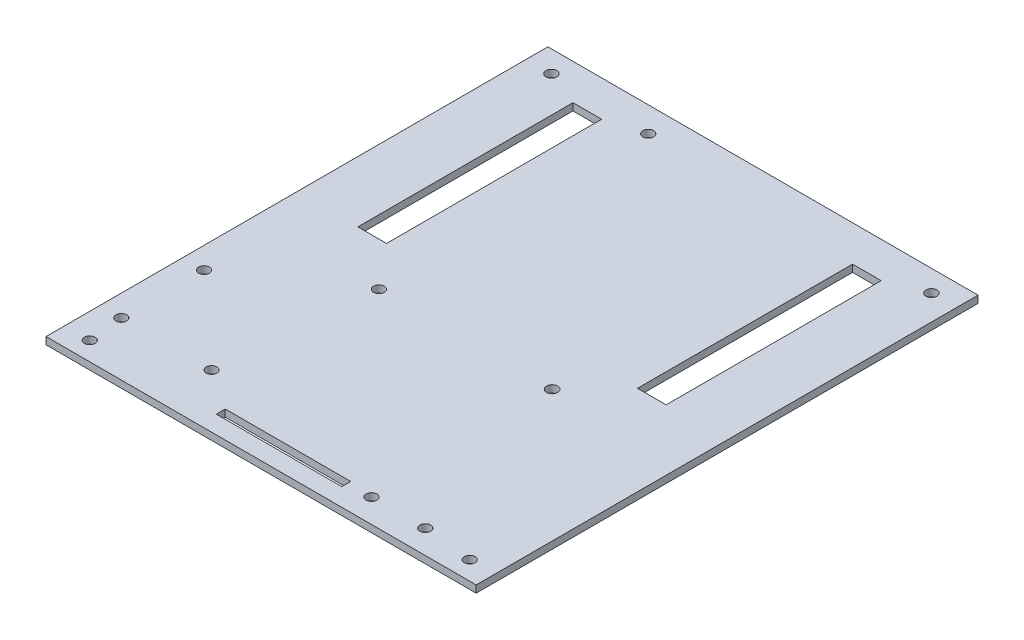
SolidWorks part; units mm, degrees
ref_plane "Front Plane" through (0, 0, 0) normal (0, 0, 1) x (1, 0, 0)
ref_plane "Top Plane" through (0, 0, 0) normal (0, 1, 0) x (1, 0, 0)
ref_plane "Right Plane" through (0, 0, 0) normal (1, 0, 0) x (0, 0, -1)
sketch "Sketch1" plane through (0, 0, 0) normal (0, 1, 0) x (1, 0, 0)
  line L1 (60, -70) -> (-60, -70)
  line L2 (60, -70) -> (60, 70)
  line L3 (60, 70) -> (-60, 70)
  line L4 (-60, -70) -> (-60, 70)
  line L5 (60, -70) -> (-60, 70) construction
  line L6 (60, 70) -> (-60, -70) construction
  point P0 (0, 0)
  dimension "D1" = 140
  dimension "D2" = 120
extrude "Boss-Extrude1" add sketch "Sketch1" along normal blind 2
sketch "Sketch2" plane through (0, 2, 0) normal (0, 1, 0) x (1, 0, 0)
  line L0 (0, 0) -> (0, 70) construction
  line L1 (60, 70) -> (-60, 70) construction
  line L2 (0, 0) -> (-60, 0) construction
  line L3 (-60, 70) -> (-60, -70) construction
  line L4 (-60, -70) -> (60, -70) construction
  circle A0 centre (-53, 64) radius 1.525
  circle A1 centre (-53, -64.8) radius 1.5
  circle A2 centre (53, 64) radius 1.525
  circle A3 centre (53, -64.8) radius 1.5
  dimension "D1" = 3.05
  dimension "D2" = 6
  dimension "D3" = 7
  dimension "D4" = 3
  dimension "D5" = 5.2
  dimension "D6" = 7
extrude "Cut-Extrude1" cut sketch "Sketch2" against normal blind 2
sketch "Sketch4" plane through (0, 2, 0) normal (0, 1, 0) x (1, 0, 0)
  line L0 (60, 70) -> (-60, 70) construction
  line L1 (-60, 70) -> (-60, -70) construction
  line L2 (0, 0) -> (0, 70) construction
  line L3 (-35, 60) -> (-43, 60)
  line L4 (-35, 60) -> (-35, 0)
  line L5 (-35, 0) -> (-43, 0)
  line L6 (-43, 60) -> (-43, 0)
  line L7 (-35, 60) -> (-43, 0) construction
  line L8 (-35, 0) -> (-43, 60) construction
  line L9 (35, 0) -> (43, 0)
  line L10 (35, 60) -> (35, 0)
  line L11 (43, 60) -> (43, 0)
  line L12 (35, 60) -> (43, 60)
  circle A0 centre (-25, 63) radius 1.5
  circle A1 centre (-25, -12.13) radius 1.5
  circle A2 centre (23.33, -12.13) radius 1.55
  point P10 (-39, 30)
  dimension "D1" = 3
  dimension "D2" = 3
  dimension "D4" = 7
  dimension "D5" = 35
  dimension "D6" = 35
  dimension "D7" = 3.1
  dimension "D9" = 82.13
  dimension "D3" = 75.13
  dimension "D8" = 48.33
  dimension "D10" = 8
  dimension "D11" = 10
  dimension "D12" = 60
  dimension "D13" = 17
extrude "Cut-Extrude2" cut sketch "Sketch4" against normal through all
sketch "Sketch5" plane through (0, 2, 0) normal (0, 1, 0) x (1, 0, 0)
  line L0 (-60, 70) -> (-60, -70) construction
  line L1 (-60, -70) -> (60, -70) construction
  line L3 (17.5, -65) -> (-17.5, -65)
  line L4 (17.5, -65) -> (17.5, -62.5)
  line L5 (17.5, -62.5) -> (-17.5, -62.5)
  line L6 (-17.5, -65) -> (-17.5, -62.5)
  line L7 (17.5, -65) -> (-17.5, -62.5) construction
  line L8 (17.5, -62.5) -> (-17.5, -65) construction
  circle A0 centre (-54, -55) radius 1.5
  circle A1 centre (-28.82, -55) radius 1.5
  circle A2 centre (-54, -31.9) radius 1.5
  circle A3 centre (24.1836, -63.3826) radius 1.5
  circle A4 centre (39.1836, -63.3826) radius 1.5
  point P10 (0, -63.75)
  point P20 (0, 0)
  dimension "D1" = 3
  dimension "D2" = 3
  dimension "D4" = 3
  dimension "D8" = 15
  dimension "D9" = 15
  dimension "D3" = 25.18
  dimension "D5" = 23.1
  dimension "D6" = 6
  dimension "D7" = 6
  dimension "D10" = 5
  dimension "D11" = 2.5
  dimension "D12" = 35
  dimension "D13" = 0
extrude "Cut-Extrude3" cut sketch "Sketch5" against normal through all
